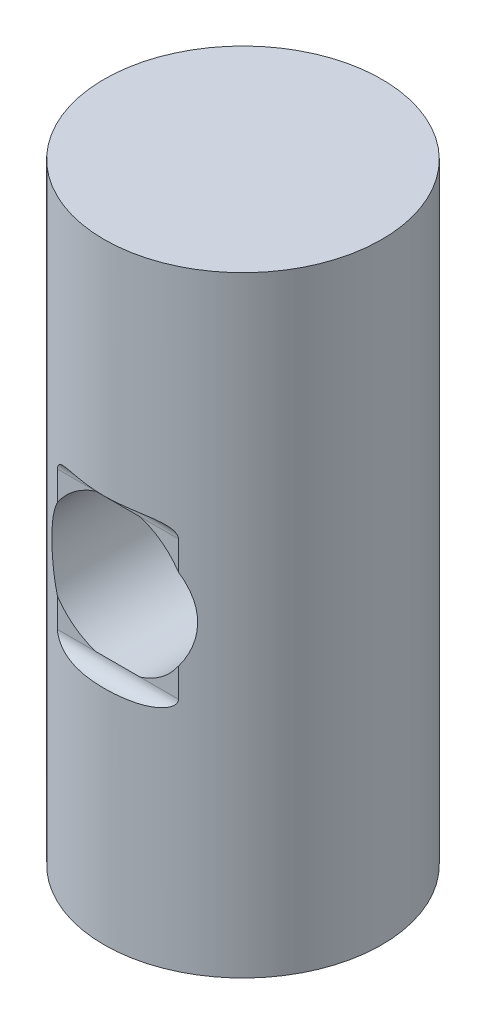
SolidWorks part; units mm, degrees
ref_plane "正面" through (0, 0, 0) normal (0, 0, 1) x (1, 0, 0)
ref_plane "平面" through (0, 0, 0) normal (0, 1, 0) x (1, 0, 0)
ref_plane "右側面" through (0, 0, 0) normal (1, 0, 0) x (0, 0, -1)
sketch "ｽｹｯﾁ1" plane through (0, 0, 0) normal (0, 1, 0) x (1, 0, 0)
  circle A0 centre (0, 0) radius 10
  dimension "D1" = 20
extrude "ﾎﾞｽ - 押し出し1" add sketch "ｽｹｯﾁ1" along normal mid plane 44
sketch "ｽｹｯﾁ4" plane through (0, 0, 0) normal (1, 0, 0) x (0, 0, -1)
  line L0 (-10, -22) -> (10, -22) construction
  line L1 (-12.5256, 6) -> (-9, 6)
  line L2 (-12.5256, 6) -> (-12.5256, -6)
  line L3 (-12.5256, -6) -> (-9, -6)
  line L4 (-9, 6) -> (-9, -6)
  line L5 (0, 24.8415) -> (0, -25.9203) construction
  line L6 (9, 6) -> (9, -6)
  line L7 (12.5256, -6) -> (9, -6)
  line L8 (12.5256, 6) -> (12.5256, -6)
  line L10 (12.5256, 6) -> (9, 6)
  dimension "D1" = 12
  dimension "D2" = 16
  dimension "D3" = 9
extrude "ｶｯﾄ - 押し出し1" cut sketch "ｽｹｯﾁ4" against normal mid plane 44
fillet "ﾌｨﾚｯﾄ1" radius 1 4 edges at (0, -6, -9) (0, 6, -9) (0, -6, 9) (0, 6, 9)
sketch "Sketch1" plane through (0, 0, 9) normal (0, 0, 1) x (1, 0, 0)
  point P0 (0, 0)
hole_wizard "M12x1.5 ねじ穴1" positions "Sketch3" profile "Sketch2" tap size "M12x1.5" standard "JIS" end condition through all
sketch "Sketch3" plane through (0, 0, 9) normal (0, 0, 1) x (1, 0, 0)
  point P1 (0, 0)
sketch "Sketch2" plane through (0, 0, 9) normal (1, 0, 0) x (0, -1, 0)
  line L0 (0, 0) -> (0, 19)
  line L1 (0, 19) -> (5.25, 19)
  line L2 (5.25, 19) -> (5.25, 0)
  line L5 (5.25, 0) -> (0, 0)
  line L11 (0, -6.35) -> (0, 107.95) construction
  dimension "ねじ山の主要直径" = 10.5
  dimension "次ｻｰﾌｪｽまでのねじ下穴ﾄﾞﾘﾙの深さ" = 19
